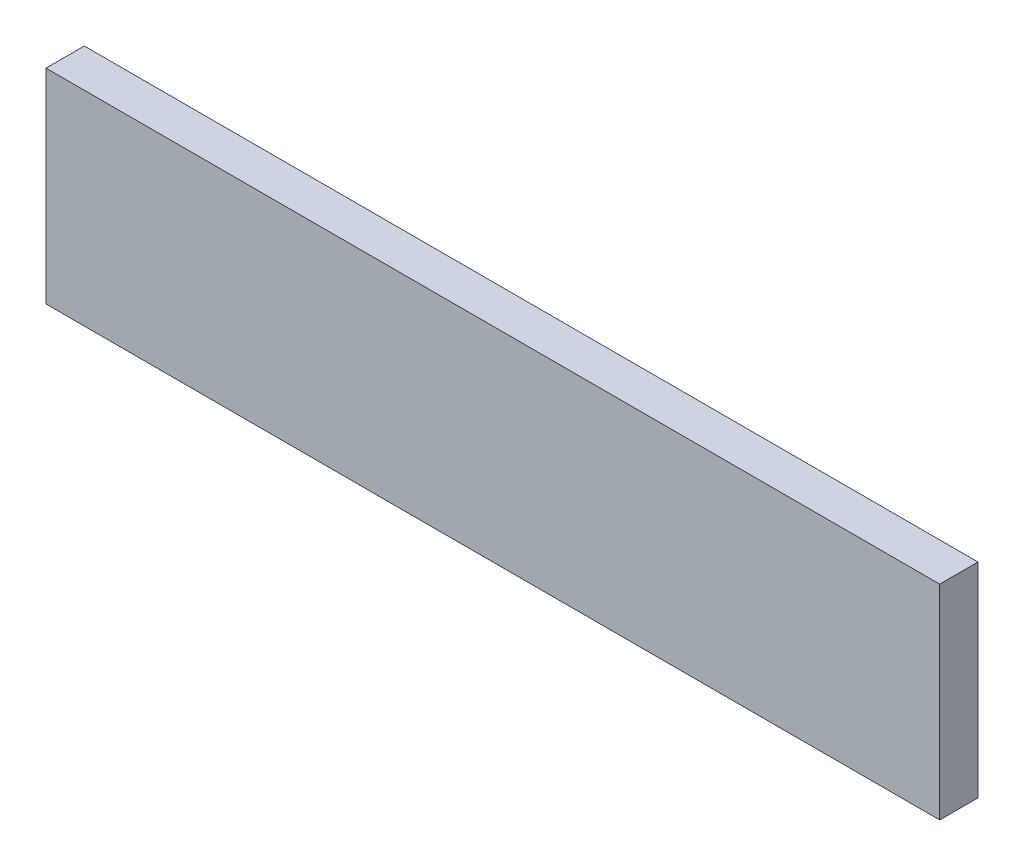
SolidWorks part; units mm, degrees
ref_plane "Ön Düzlem" through (0, 0, 0) normal (0, 0, 1) x (1, 0, 0)
ref_plane "Üst Düzlem" through (0, 0, 0) normal (0, 1, 0) x (1, 0, 0)
ref_plane "Sağ Düzlem" through (0, 0, 0) normal (1, 0, 0) x (0, 0, -1)
sketch "Çizim1" plane through (0, 0, 0) normal (0, 0, 1) x (1, 0, 0)
  line L1 (0, 0) -> (350, 0)
  line L2 (0, 0) -> (0, -80)
  line L3 (0, -80) -> (350, -80)
  line L4 (350, 0) -> (350, -80)
  dimension "D1" = 350
  dimension "D2" = 80
base flange "Taban-Flanş1" sketch "Çizim1" thickness 15 reverse thickness direction no parameters "D1"=8
sketch "Büküm-Çizgileri1" [suppressed] plane through (0, 0, 0) normal (0, 1, 0) x (1, 0, 0)
sketch "Sınırlandırma-Kutusu1" [suppressed] plane through (0, 0, 0) normal (0, 1, 0) x (1, 0, 0)
sheet metal parameters "Sac-Levha1" thickness 15 parameters "D1"=8
flat pattern "Düz-Çoğaltma1" [suppressed]
sketch "Büküm-Çizgileri2" plane through (0, 0, 0) normal (0, 1, 0) x (1, 0, 0)
sketch3d "Sınırlandırma-Kutusu2" [suppressed]
  line L0 (0, -80, 0) -> (350, -80, 0) construction
  line L1 (0, 0, 0) -> (350, 0, 0) construction
  line L2 (0, -80, 0) -> (0, 0, 0) construction
  line L3 (350, -80, 0) -> (350, 0, 0) construction
